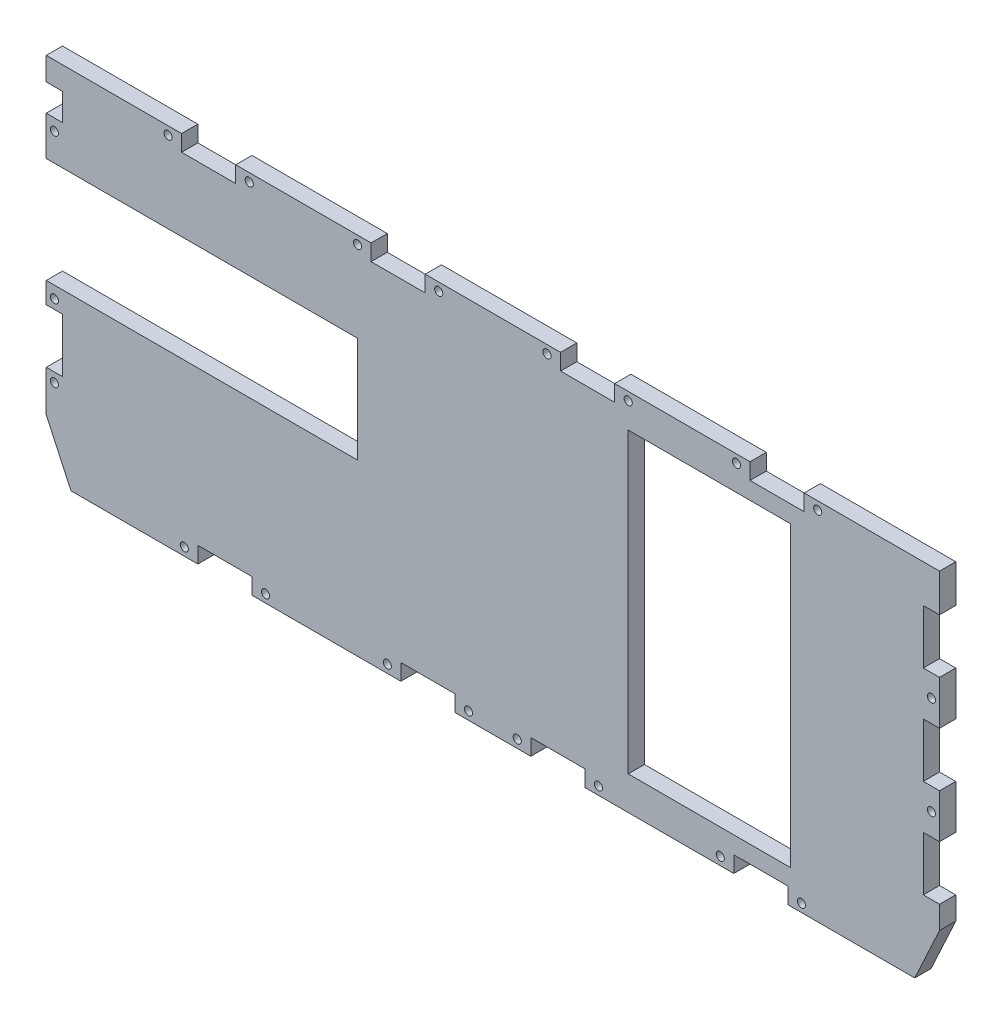
SolidWorks part; units mm, degrees
ref_plane "Plan de face" through (0, 0, 0) normal (0, 0, 1) x (1, 0, 0)
ref_plane "Plan de dessus" through (0, 0, 0) normal (0, 1, 0) x (1, 0, 0)
ref_plane "Plan de droite" through (0, 0, 0) normal (1, 0, 0) x (0, 0, -1)
sketch "Esquisse1" plane through (0, 0, 0) normal (0, 0, 1) x (1, 0, 0)
  line L0 (0, 124.9429) -> (0, -204.46) construction
  line L1 (-165, 96.73) -> (165, 96.73)
  line L2 (165, 96.73) -> (165, -18.27)
  line L3 (165, -18.27) -> (123, -109.0224)
  line L4 (123, -109.0224) -> (-123, -109.0224)
  line L5 (-211.9802, 0) -> (248.5953, 0) construction
  line L6 (-123, -109.0224) -> (-165, -18.27)
  line L7 (-165, -18.27) -> (-165, 96.73)
  dimension "D2" = 165
  dimension "D3" = 330
  dimension "D4" = 100
  dimension "D5" = 115
  dimension "D6" = 100
  dimension "D7" = 246
  dimension "D8" = 205.7524
  dimension "D9" = 96.73
  dimension "D10" = 115
extrude "Boss.-Extru.1" add sketch "Esquisse1" along normal blind 6
sketch "Esquisse3" plane through (0, 0, 0) normal (0, 0, -1) x (-1, 0, 0)
  line L0 (165, 96.73) -> (165, -18.27) construction
  line L1 (165, -3.06) -> (159, -3.06)
  line L2 (165, -3.06) -> (165, 16.94)
  line L3 (165, 16.94) -> (159, 16.94)
  line L4 (159, -3.06) -> (159, 16.94)
  line L5 (123, -109.0224) -> (-123, -109.0224) construction
  line L6 (165, 78.2326) -> (159, 78.2326)
  line L7 (165, 78.2326) -> (165, 88.2326)
  line L8 (165, 88.2326) -> (159, 88.2326)
  line L9 (159, 78.2326) -> (159, 88.2326)
  line L10 (-14, -38.02) -> (-14, -32.02)
  line L11 (109, -38.02) -> (89, -38.02)
  line L12 (109, -38.02) -> (109, -32.02)
  line L13 (109, -32.02) -> (89, -32.02)
  line L15 (0, -209.4812) -> (0, 177.1799) construction
  line L16 (-110, 84.355) -> (-50, 84.355)
  line L17 (-165, 82.73) -> (-159, 82.73)
  line L18 (89, -38.02) -> (89, -32.02)
  line L19 (34, -38.02) -> (14, -38.02)
  line L20 (34, -38.02) -> (34, -32.02)
  line L21 (34, -32.02) -> (14, -32.02)
  line L22 (-165, 82.73) -> (-165, 62.73)
  line L23 (-165, 62.73) -> (-159, 62.73)
  line L24 (-159, 82.73) -> (-159, 62.73)
  line L25 (-165, 46.44) -> (-159, 46.44)
  line L26 (-165, 46.44) -> (-165, 26.44)
  line L27 (-165, 26.44) -> (-159, 26.44)
  line L28 (-159, 46.44) -> (-159, 26.44)
  line L29 (-165, 10.15) -> (-159, 10.15)
  line L30 (-165, 96.73) -> (165, 96.73) construction
  line L31 (115, 96.73) -> (95, 96.73)
  line L32 (115, 96.73) -> (115, 90.73)
  line L33 (115, 90.73) -> (95, 90.73)
  line L34 (95, 96.73) -> (95, 90.73)
  line L35 (-25, 96.73) -> (-25, 90.73)
  line L36 (45, 96.73) -> (25, 96.73)
  line L37 (45, 96.73) -> (45, 90.73)
  line L38 (45, 90.73) -> (25, 90.73)
  line L39 (25, 96.73) -> (25, 90.73)
  line L40 (-45, 90.73) -> (-25, 90.73)
  line L41 (-45, 96.73) -> (-45, 90.73)
  line L42 (-45, 96.73) -> (-25, 96.73)
  line L43 (-95, 96.73) -> (-95, 90.73)
  line L44 (-115, 90.73) -> (-95, 90.73)
  line L45 (-115, 96.73) -> (-115, 90.73)
  line L46 (-115, 96.73) -> (-95, 96.73)
  line L47 (-165, 10.15) -> (-165, -9.85)
  line L48 (14, -38.02) -> (14, -32.02)
  line L49 (-34, -32.02) -> (-14, -32.02)
  line L50 (-34, -38.02) -> (-34, -32.02)
  line L51 (-34, -38.02) -> (-14, -38.02)
  line L52 (-165, -9.85) -> (-159, -9.85)
  line L53 (165, 63.73) -> (50, 63.73)
  line L54 (165, 63.73) -> (165, 24.73)
  line L55 (165, 24.73) -> (50, 24.73)
  line L56 (-159, 10.15) -> (-159, -9.85)
  line L57 (-89, -38.02) -> (-89, -32.02)
  line L58 (-109, -32.02) -> (-89, -32.02)
  line L59 (-109, -38.02) -> (-109, -32.02)
  line L60 (-109, -38.02) -> (-89, -38.02)
  line L62 (-110, 84.355) -> (-110, -25.645)
  line L63 (-110, -25.645) -> (-50, -25.645)
  line L64 (-50, 84.355) -> (-50, -25.645)
  line L65 (-165, -18.27) -> (-165, 96.73) construction
  line L66 (50, 63.73) -> (50, 24.73)
  dimension "D1" = 20
  dimension "D2" = 6
  dimension "D3" = 6
  dimension "D4" = 10
  dimension "D5" = 6
  dimension "D6" = 20
  dimension "D7" = 60
  dimension "D8" = 55
  dimension "D9" = 8.4974
  dimension "D10" = 20
  dimension "D11" = 20
  dimension "D12" = 50
  dimension "D13" = 50
  dimension "D14" = 6
  dimension "D15" = 110
  dimension "D16" = 56
  dimension "D17" = 55
  dimension "D18" = 20
  dimension "D19" = 20
  dimension "D20" = 20
  dimension "D21" = 6
  dimension "D22" = 6
  dimension "D23" = 20
  dimension "D24" = 71.0024
  dimension "D25" = 71.0024
  dimension "D26" = 33
  dimension "D27" = 39
  dimension "D28" = 115
  dimension "D29" = 6.375
  dimension "D30" = 15.21
  dimension "D31" = 6
  dimension "D32" = 6
  dimension "D33" = 6
  dimension "D34" = 14
  dimension "D35" = 16.29
  dimension "D36" = 16.29
extrude "Enlèv. mat.-Extru.2" cut sketch "Esquisse3" against normal blind 6
sketch "Esquisse4" plane through (0, 0, 0) normal (0, 0, -1) x (-1, 0, 0)
  line L0 (159, 78.2326) -> (165, 78.2326) construction
  line L1 (115, 90.73) -> (115, 96.73) construction
  line L2 (120.102, -35.02) -> (4.7601, -35.02) construction
  line L3 (14, -32.02) -> (14, -38.02) construction
  line L4 (34, -38.02) -> (34, -32.02) construction
  line L5 (89, -32.02) -> (89, -38.02) construction
  line L7 (109, -38.02) -> (109, -32.02) construction
  line L8 (165, 78.2326) -> (165, 63.73) construction
  line L9 (-120.102, -35.02) -> (-4.7601, -35.02) construction
  line L11 (143.8632, 93.73) -> (-5, 93.73) construction
  line L12 (45, 96.73) -> (95, 96.73) construction
  line L13 (-162, -27.3544) -> (-162, 100.425) construction
  line L14 (95, 96.73) -> (95, 90.73) construction
  line L15 (45, 90.73) -> (45, 96.73) construction
  line L16 (25, 96.73) -> (25, 90.73) construction
  line L17 (0, 142.2997) -> (0, -202.2086) construction
  line L18 (-165, -18.27) -> (-165, -9.85) construction
  line L19 (-80, 84.355) -> (-80, -25.645) construction
  line L21 (165, 16.94) -> (159, 16.94) construction
  line L22 (162, -8.8216) -> (162, 103.5789) construction
  line L25 (-50, 84.355) -> (-110, 84.355) construction
  line L26 (-110, -25.645) -> (-50, -25.645) construction
  line L27 (-159, 46.44) -> (-165, 46.44) construction
  line L28 (-165, 26.44) -> (-159, 26.44) construction
  line L31 (159, -3.06) -> (165, -3.06) construction
  circle A0 centre (162, 20.335) radius 1.5
  circle A1 centre (114, -35.02) radius 1.5
  circle A2 centre (162, 73.9826) radius 1.5
  circle A3 centre (84, -35.02) radius 1.5
  circle A4 centre (39, -35.02) radius 1.5
  circle A5 centre (162, -6.46) radius 1.5
  circle A6 centre (9, -35.02) radius 1.5
  circle A7 centre (-9, -35.02) radius 1.5
  circle A8 centre (-39, -35.02) radius 1.5
  circle A9 centre (-84, -35.02) radius 1.5
  circle A10 centre (120, 93.73) radius 1.5
  circle A11 centre (-114, -35.02) radius 1.5
  circle A12 centre (90, 93.73) radius 1.5
  circle A14 centre (50, 93.73) radius 1.5
  circle A15 centre (20, 93.73) radius 1.5
  circle A16 centre (-162, 18.29) radius 1.5
  circle A17 centre (-162, 54.585) radius 1.5
  circle A18 centre (-20, 93.73) radius 1.5
  circle A19 centre (-50, 93.73) radius 1.5
  circle A20 centre (-90, 93.73) radius 1.5
  circle A21 centre (-120, 93.73) radius 1.5
  dimension "D3" = 3
  dimension "D10" = 3
  dimension "D11" = 3
  dimension "D12" = 3
  dimension "D13" = 5
  dimension "D14" = 5
  dimension "D18" = 3
  dimension "D19" = 3
  dimension "D29" = 3
  dimension "D30" = 8.15
  dimension "D31" = 3
  dimension "D33" = 3
  dimension "D34" = 3
  dimension "D40" = 5
  dimension "D5" = 3.395
  dimension "D8" = 5
  dimension "D15" = 5
  dimension "D16" = 5
  dimension "D20" = 3.4
  dimension "D17" = 3
  dimension "D21" = 3
  dimension "D22" = 3
  dimension "D27" = 8.145
  dimension "D9" = 3
  dimension "D7" = 3
  dimension "D6" = 4.25
  dimension "D26" = 3
  dimension "D28" = 3
  dimension "D38" = 5
  dimension "D42" = 5
extrude "Enlèv. mat.-Extru.3" cut sketch "Esquisse4" against normal blind 6
sketch "Esquisse5" plane through (0, 0, 0) normal (0, 0, -1) x (-1, 0, 0)
  line L0 (45, 96.73) -> (95, 96.73) construction
  line L1 (209.7155, -38.02) -> (-246.3297, -38.02)
  line L2 (209.7155, -38.02) -> (209.7155, -174.249)
  line L3 (209.7155, -174.249) -> (-246.3297, -174.249)
  line L4 (-246.3297, -38.02) -> (-246.3297, -174.249)
  dimension "D1" = 134.75
extrude "Enlèv. mat.-Extru.4" cut sketch "Esquisse5" against normal blind 6
